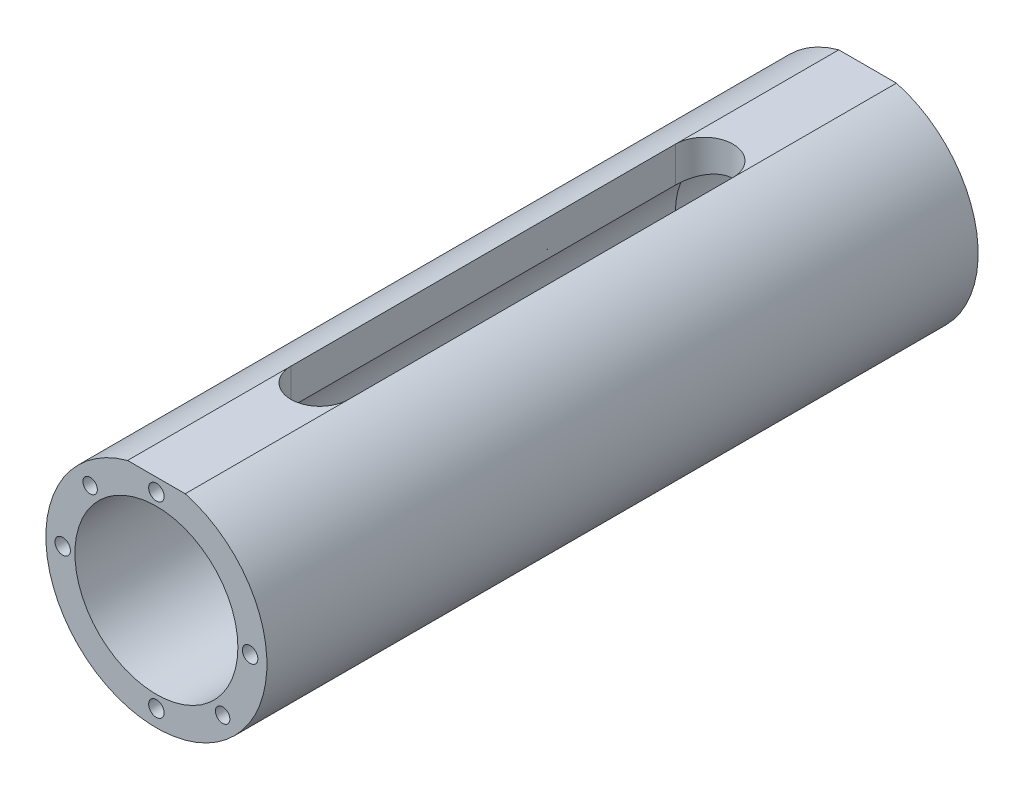
SolidWorks part; units mm, degrees
material "6061 Alloy"
ref_plane "Front" through (0, 0, 0) normal (0, 0, 1) x (1, 0, 0)
ref_plane "Top" through (0, 0, 0) normal (0, 1, 0) x (1, 0, 0)
ref_plane "Right" through (0, 0, 0) normal (1, 0, 0) x (0, 0, -1)
sketch "Bolt circle" plane through (0, 0, 0) normal (0, 0, 1) x (1, 0, 0)
  line L0 (0, 36.5125) -> (0, 25.4) construction
  circle A0 centre (0, 0) radius 36.5125
  circle A1 centre (0, 0) radius 25.4
  circle A2 centre (0, 0) radius 30.9562 construction
  point P7 (0, 30.9562)
  dimension "D1" = 73.025
  dimension "D2" = 50.8
  dimension "D3" = 61.9125
extrude "Base shape" add sketch "Bolt circle" along normal mid plane 234.95
ref_axis "Axis" through (0, 0, -80.9) along (0, 0, 1)
hole_wizard "1/4-20 #1" positions "3DSketch5" profile "Sketch10" tap size "1/4-20" standard "Ansi Inch"
sketch3d "3DSketch5"
  point P0 (0, 30.9562, -117.475)
sketch "Sketch10" plane through (0, 30.9562, -117.475) normal (1, 0, 0) x (0, 1, 0)
  line L0 (0, 0) -> (0, 20.5838)
  line L1 (0, 20.5838) -> (2.5527, 19.05)
  line L2 (2.5527, 19.05) -> (2.5527, 0.6223)
  line L3 (2.5527, 0.6223) -> (3.175, 0)
  line L5 (3.175, 0) -> (0, 0)
  line L6 (-2.5527, 0.6223) -> (-3.175, 0) construction
  line L10 (0, 20.5838) -> (-2.5527, 19.05) construction
  line L11 (0, -6.35) -> (0, 107.95) construction
  dimension "Tap Drill Dia." = 5.1054
  dimension "Tap Drill Depth" = 19.05
  dimension "Near C'Sink Dia." = 6.35
  dimension "Near C'Sink Angle" = 90
  dimension "Drill Angle" = 118
cosmetic thread "Hole Thread1" parameters "D1"=12.7, "D2"=6.35
hole_wizard "1/4-20 #2" positions "3DSketch6" profile "Sketch11" tap size "1/4-20" standard "Ansi Inch"
sketch3d "3DSketch6"
  point P0 (0, 30.9562, 117.475)
sketch "Sketch11" plane through (0, 30.9562, 117.475) normal (1, 0, 0) x (0, -1, 0)
  line L0 (0, 0) -> (0, 20.5838)
  line L1 (0, 20.5838) -> (2.5527, 19.05)
  line L2 (2.5527, 19.05) -> (2.5527, 0)
  line L5 (2.5527, 0) -> (0, 0)
  line L10 (0, 20.5838) -> (-2.5527, 19.05) construction
  line L11 (0, -6.35) -> (0, 107.95) construction
  dimension "Tap Drill Dia." = 5.1054
  dimension "Tap Drill Depth" = 19.05
  dimension "Drill Angle" = 118
cosmetic thread "Hole Thread2" parameters "D1"=12.7, "D2"=6.35
pattern_circular "Bolt pattern" count 4 over 360 about axis through (0, 0, -80.9) along (0, 0, 1) of "1/4-20 #1", "1/4-20 #2"
sketch "Sketch14" plane through (0, 0, 0) normal (0, 1, 0) x (1, 0, 0)
  line L1 (-25.4, -117.475) -> (25.4, -117.475) construction
  line L2 (-9.525, 63.5) -> (-9.525, -63.5)
  line L3 (36.5125, 117.475) -> (-36.5125, 117.475) construction
  line L4 (9.525, 63.5) -> (9.525, -63.5)
  arc A0 (9.525, 63.5) -> (-9.525, 63.5) centre (0, 63.5) ccw
  arc A1 (-9.525, -63.5) -> (9.525, -63.5) centre (0, -63.5) ccw
  dimension "D2" = 9.525
  dimension "D1" = 53.975
  dimension "D3" = 53.975
extrude "Slot" cut sketch "Sketch14" along normal through all
sketch "Sketch17" plane through (0, 0, 117.475) normal (0, 0, 1) x (1, 0, 0)
  circle A0 centre (0, 0) radius 26.924
  circle A1 centre (-30.9562, 0) radius 3.175 construction
  dimension "D1" = 53.848
  dimension "D2" = 6.35
extrude "Inner Step" cut sketch "Sketch17" against normal blind 38.1
mirror "Step Mirror" about plane through (0, 0, 0) normal (0, 0, 1) of "Inner Step"
ref_plane "Slot Plane" through (0, 35.2482, 0) normal (0, 1, 0) x (-1, 0, 0)
sketch "Sketch20" plane through (0, 0, 0) normal (0, 0, 1) x (1, 0, 0)
  line L0 (10.4775, 35.2482) -> (-10.4775, 35.2482) construction
  line L1 (-18.7704, 36.9527) -> (18.6724, 36.9527)
  line L2 (-18.7704, 36.9527) -> (-18.7704, 35.2482)
  line L3 (-18.7704, 35.2482) -> (18.6724, 35.2482)
  line L4 (18.6724, 36.9527) -> (18.6724, 35.2482)
extrude "Extrude1" cut sketch "Sketch20" against normal through all and the other way through all
hole_wizard "Alignment_pin_holes" positions "Sketch24" profile "Sketch23" hole size "3/16" standard "Ansi Inch"
sketch "Sketch24" plane through (0, 0, 117.475) normal (0, 0, 1) x (1, 0, 0)
  line L0 (21.8894, -21.8894) -> (-21.8894, 21.8894) construction
  line L2 (50, 0) -> (-50, 0) construction
  circle A0 centre (0, 0) radius 30.9562 construction
  point P0 (-21.8894, 21.8894)
  point P1 (21.8894, -21.8894)
  dimension "D1" = 45
sketch "Sketch23" plane through (-21.8894, 21.8894, 117.475) normal (1, 0, 0) x (0, -1, 0)
  line L0 (0, 0) -> (0, 14.1308)
  line L1 (0, 14.1308) -> (2.3812, 12.7)
  line L2 (2.3812, 12.7) -> (2.3812, 0)
  line L5 (2.3812, 0) -> (0, 0)
  line L10 (0, 14.1308) -> (-2.3813, 12.7) construction
  line L11 (0, -6.35) -> (0, 107.95) construction
  dimension "Hole Dia." = 4.7625
  dimension "Hole Depth" = 12.7
  dimension "Drill Angle" = 118
hole_wizard "3/16 (0.1875) Diameter Hole1" positions "Sketch26" profile "Sketch25" hole size "3/16" standard "Ansi Inch"
sketch "Sketch26" plane through (0, 0, -117.475) normal (0, 0, -1) x (-1, 0, 0)
  line L0 (-21.8894, 21.8894) -> (21.8894, -21.8894) construction
  line L1 (50, 0) -> (-50, 0) construction
  circle A0 centre (0, 0) radius 30.9562 construction
  point P0 (-21.8894, 21.8894)
  point P1 (21.8894, -21.8894)
  dimension "D1" = 45
sketch "Sketch25" plane through (21.8894, 21.8894, -117.475) normal (1, 0, 0) x (0, 1, 0)
  line L0 (0, 0) -> (0, 14.1308)
  line L1 (0, 14.1308) -> (2.3812, 12.7)
  line L2 (2.3812, 12.7) -> (2.3812, 0)
  line L5 (2.3812, 0) -> (0, 0)
  line L10 (0, 14.1308) -> (-2.3812, 12.7) construction
  line L11 (0, -6.35) -> (0, 107.95) construction
  dimension "Hole Dia." = 4.7625
  dimension "Hole Depth" = 12.7
  dimension "Drill Angle" = 118
